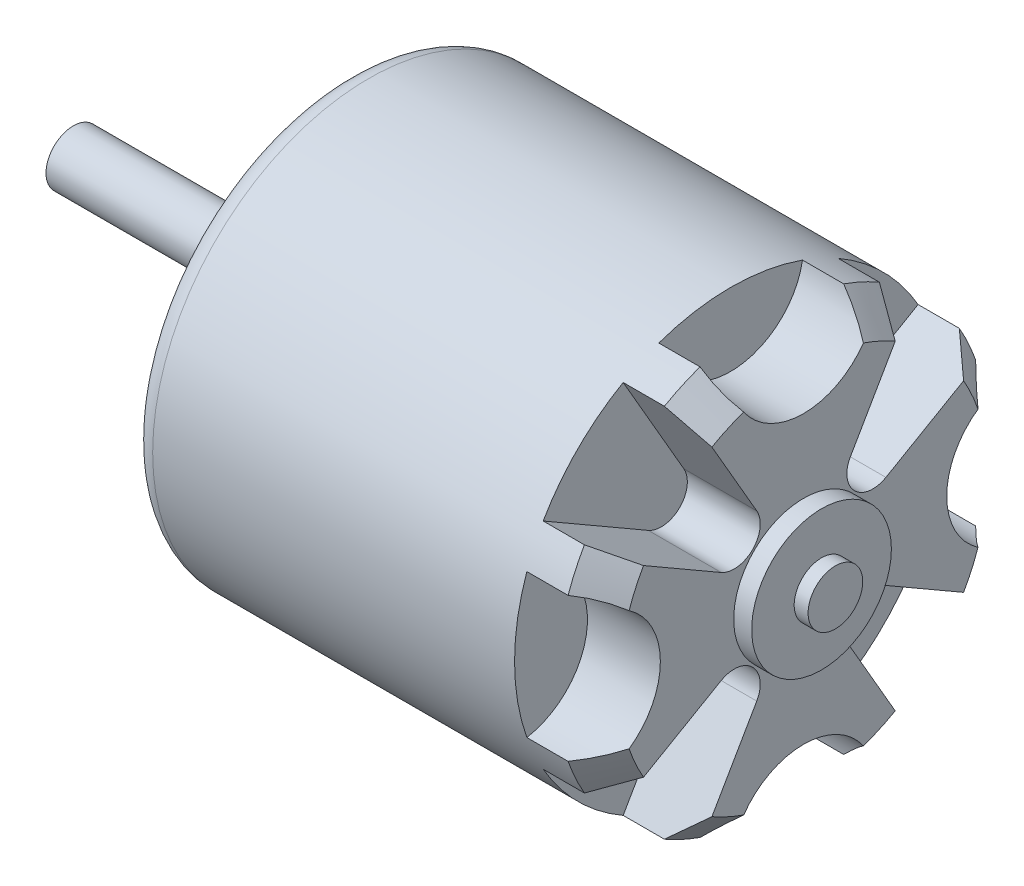
SolidWorks part; units mm, degrees
ref_plane "Front Plane" through (0, 0, 0) normal (0, 0, 1) x (1, 0, 0)
ref_plane "Top Plane" through (0, 0, 0) normal (0, 1, 0) x (1, 0, 0)
ref_plane "Right Plane" through (0, 0, 0) normal (1, 0, 0) x (0, 0, -1)
sketch "Sketch1" plane through (0, 0, 0) normal (1, 0, 0) x (0, 0, -1)
  circle A0 centre (0, 0) radius 31.623
  dimension "D1" = 63.246
extrude "Boss-Extrude1" add sketch "Sketch1" along normal blind 66.802
sketch "Sketch2" plane through (66.802, 0, 0) normal (1, 0, 0) x (0, 0, -1)
  line L0 (-31.623, 0) -> (31.623, 0) construction
  line L1 (0, 0) -> (-22.3608, 22.3608) construction
  line L2 (-12.0527, 6.8481) -> (-27.434, 15.7286)
  line L3 (-6.8481, 12.0527) -> (-15.7286, 27.434)
  line L4 (12.0527, 6.8481) -> (27.434, 15.7286)
  line L5 (6.8481, 12.0527) -> (15.7286, 27.434)
  line L6 (6.8481, -12.0527) -> (15.7286, -27.434)
  line L7 (12.0527, -6.8481) -> (27.434, -15.7286)
  line L8 (-12.0527, -6.8481) -> (-27.434, -15.7286)
  line L9 (-6.8481, -12.0527) -> (-15.7286, -27.434)
  arc A0 (-10.5151, 29.8236) -> (10.5151, 29.8236) centre (0, 31.623) ccw
  circle A1 centre (0, 0) radius 31.623 construction
  arc A2 (-29.8236, -10.5151) -> (-29.8236, 10.5151) centre (-31.623, 0) ccw
  arc A3 (29.8236, 10.5151) -> (29.8236, -10.5151) centre (31.623, 0) ccw
  arc A4 (10.5151, -29.8236) -> (-10.5151, -29.8236) centre (0, -31.623) ccw
  circle A5 centre (0, 0) radius 10.541
  arc A6 (-12.8418, 12.8418) -> (-6.8481, 12.0527) centre (-10.1477, 10.1477) ccw
  arc A7 (6.8481, 12.0527) -> (12.0527, 6.8481) centre (10.1477, 10.1477) ccw
  arc A8 (12.0527, -6.8481) -> (6.8481, -12.0527) centre (10.1477, -10.1477) ccw
  arc A9 (-6.8481, -12.0527) -> (-12.0527, -6.8481) centre (-10.1477, -10.1477) ccw
  circle A10 centre (0, 0) radius 31.623
  point P28 (0, 0)
  point P45 (0, 0)
  circle M5 centre (0, 0) radius 31.623
  dimension "D1" = 21.336
  dimension "D2" = 21.336
  dimension "D3" = 21.336
  dimension "D4" = 21.336
  dimension "D8" = 21.082
  dimension "D10" = 7.62
  dimension "D5" = 31.623
  dimension "D6" = 31.623
  dimension "D7" = 31.623
  dimension "D9" = 45
  dimension "D12" = 15
  dimension "D13" = 30
  dimension "D11" = 4
  dimension "D14" = 4
extrude "Cut-Extrude1" cut sketch "Sketch2" against normal blind 10.668 contours A9 L8 L9 M5 | L7 A8 L6 M5 | L5 A7 L4 M5 | A3 M5 | L2 A6 L3 M5 | A0 M5 | A2 M5 | A4 M5 region at (66.802, 16.08, 16.08) region at (66.802, 0, 26.787) region at (66.802, 16.08, -16.08) region at (66.802, -16.08, 16.08) region at (66.802, 26.787, 0) region at (66.802, -16.08, -16.08) region at (66.802, 0, -26.787) region at (66.802, -26.787, 0)
chamfer "Chamfer1" distance 4.6355 angle 45 8 edges at (66.802, 28.7472, 13.1761) (66.802, 28.7472, -13.1761) (66.802, 13.1761, -28.7472) (66.802, -13.1761, -28.7472) (66.802, -28.7472, -13.1761) (66.802, -28.7472, 13.1761) (66.802, -13.1761, 28.7472) (66.802, 13.1761, 28.7472)
sketch "Sketch3" plane through (66.802, 0, 0) normal (1, 0, 0) x (0, 0, -1)
  circle A0 centre (0, 0) radius 10.2235
  dimension "D1" = 20.447
extrude "Boss-Extrude2" add sketch "Sketch3" along normal blind 2.6289
sketch "Sketch4" plane through (69.4309, 0, 0) normal (1, 0, 0) x (0, 0, -1)
  circle A0 centre (0, 0) radius 4
  dimension "D1" = 8
extrude "Boss-Extrude3" add sketch "Sketch4" along normal blind 2.032
sketch "Sketch5" plane through (0, 0, 0) normal (-1, 0, 0) x (0, 0, 1)
  circle A0 centre (0, 0) radius 8.7376
  dimension "D1" = 17.4752
extrude "Boss-Extrude4" add sketch "Sketch5" along normal blind 12.3698
sketch "Sketch6" plane through (-12.3698, 0, 0) normal (-1, 0, 0) x (0, 0, 1)
  circle A0 centre (0, 0) radius 4
  dimension "D1" = 8
extrude "Boss-Extrude5" add sketch "Sketch6" along normal blind 27.686
sketch "Sketch7" plane through (0, 0, 0) normal (-1, 0, 0) x (0, 0, 1)
  circle A0 centre (0, 0) radius 22.05
  dimension "D1" = 44.1
hole_wizard "M4x0.7 Tapped Hole1" positions "Sketch8" profile "Sketch9" tap size "M4x0.7" standard "ANSI Metric"
sketch "Sketch8" plane through (0, 0, 0) normal (-1, 0, 0) x (0, 0, 1)
  circle A0 centre (0, 0) radius 22.05 construction
  point P0 (0, 22.05)
  point P4 (-22.05, 0)
  point P6 (0, -22.05)
  point P8 (22.05, 0)
sketch "Sketch9" plane through (0, 22.05, 0) normal (0, 1, 0) x (0, 0, 1)
  line L0 (0, 0) -> (0, 10.8974)
  line L1 (0, 10.8974) -> (1.65, 9.906)
  line L2 (1.65, 9.906) -> (1.65, 0.375)
  line L3 (1.65, 0.375) -> (2.025, 0)
  line L5 (2.025, 0) -> (0, 0)
  line L6 (-1.65, 0.375) -> (-2.025, 0) construction
  line L10 (0, 10.8974) -> (-1.65, 9.906) construction
  line L11 (0, -6.35) -> (0, 107.95) construction
  dimension "Tap Drill Dia." = 3.3
  dimension "Tap Drill Depth" = 9.906
  dimension "Near C'Sink Dia." = 4.05
  dimension "Near C'Sink Angle" = 90
  dimension "Drill Angle" = 118
cosmetic thread "Hole Thread1" parameters "D1"=7.874, "D2"=4
cosmetic thread "Hole Thread2" parameters "D1"=7.874, "D2"=4
cosmetic thread "Hole Thread3" parameters "D1"=7.874, "D2"=4
cosmetic thread "Hole Thread4" parameters "D1"=7.874, "D2"=4
fillet "Fillet1" radius 3.175 1 edges at (0, 0, -31.623)
equation "\"D2@Sketch2\"=\"D1@Sketch2\""
equation "\"D3@Sketch2\"=\"D1@Sketch2\""
equation "\"D4@Sketch2\"=\"D1@Sketch2\""
equation "\"D13@Sketch2\"=\"D12@Sketch2\"*2"
